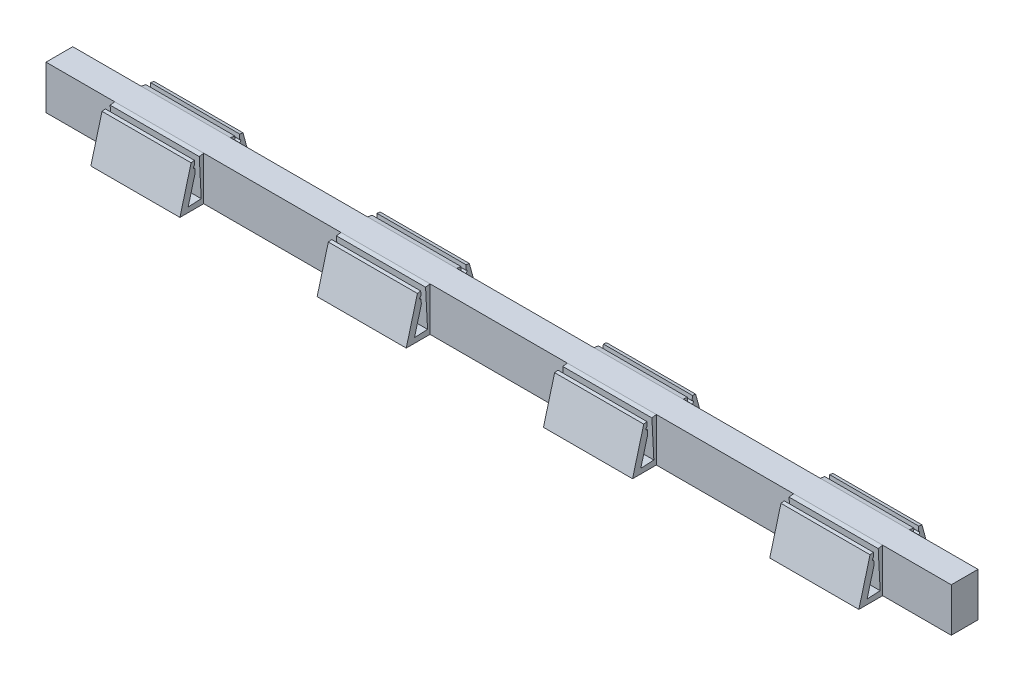
SolidWorks part; units mm, degrees
ref_plane "Front Plane" through (0, 0, 0) normal (0, 0, 1) x (1, 0, 0)
ref_plane "Top Plane" through (0, 0, 0) normal (0, 1, 0) x (1, 0, 0)
ref_plane "Right Plane" through (0, 0, 0) normal (1, 0, 0) x (0, 0, -1)
sketch "Sketch1" plane through (0, 0, 0) normal (1, 0, 0) x (0, 0, -1)
  line L0 (3.6311, 0.3059) -> (9.4677, 0) construction
  line L1 (3.904, 5.5131) -> (4.9077, 5.4605) construction
  line L2 (6.2203, 9.4885) -> (6.0816, 6.8415) construction
  line L3 (6.0816, 6.8415) -> (7.6191, 1.1033)
  line L4 (7.6191, 1.1033) -> (4.6874, 1.2569)
  line L5 (4.6874, 1.2569) -> (5.128, 9.664)
  line L6 (5.128, 9.664) -> (4.13, 9.8243)
  line L7 (4.13, 9.8243) -> (3.6311, 0.3059) construction
  line L8 (6.2203, 9.4885) -> (6.1666, 8.4646)
  line L9 (6.1352, 7.8654) -> (6.0816, 6.8415)
  line L10 (6.2203, 9.4885) -> (6.9569, 9.3702)
  line L11 (6.9569, 9.3702) -> (9.4677, 0)
  line L12 (6.1532, 1.1801) -> (6.1006, 0.1765) construction
  line L13 (1.128, 0) -> (1.128, 7.6812) construction
  line L14 (-3.8973, 1.1801) -> (-3.8447, 0.1765) construction
  line L15 (-5.3632, 1.1033) -> (-2.4314, 1.2569)
  line L16 (-3.9644, 9.4885) -> (-3.8256, 6.8415) construction
  line L17 (-1.6481, 5.5131) -> (-2.6517, 5.4605) construction
  line L18 (-1.3752, 0.3059) -> (-7.2117, 0) construction
  line L19 (-4.701, 9.3702) -> (-7.2117, 0)
  line L20 (-3.9644, 9.4885) -> (-4.701, 9.3702)
  line L21 (-3.8793, 7.8654) -> (-3.8256, 6.8415)
  line L22 (-3.9644, 9.4885) -> (-3.9107, 8.4646)
  line L23 (-1.874, 9.8243) -> (-1.3752, 0.3059) construction
  line L24 (-2.872, 9.664) -> (-1.874, 9.8243)
  line L25 (-2.4314, 1.2569) -> (-2.872, 9.664)
  line L26 (-3.8256, 6.8415) -> (-5.3632, 1.1033)
  line L27 (-1.874, 9.8243) -> (4.13, 9.8243)
  line L28 (-7.2117, 0) -> (-2.3656, 0)
  line L29 (-2.4314, 1.2569) -> (-2.3656, 0)
  line L30 (4.6874, 1.2569) -> (4.6215, 0)
  line L31 (-2.3656, 0) -> (4.6215, 0)
  line L32 (4.6215, 0) -> (9.4677, 0)
  arc A0 (6.1666, 8.4646) -> (6.1352, 7.8654) centre (6.1509, 8.165) cw
  arc A1 (-3.9107, 8.4646) -> (-3.8793, 7.8654) centre (-3.895, 8.165) ccw
  dimension "D1" = 0.3
  dimension "D2" = 1.1
  dimension "D3" = 72
  dimension "D4" = 1.5
  dimension "D5" = 8
extrude "Clip #1" add sketch "Sketch1" along normal mid plane 20 contours L28 L19 L20 L22 A1 L21 L26 L15 L25 L24 L27 L6 L5 L4 L3 L9 A0 L8 L10 L11 L32 L31
sketch "Sketch4" plane through (0, 0, 0) normal (1, 0, 0) x (0, 0, -1)
  line L0 (-1.874, 9.8243) -> (-1.874, 0)
  line L1 (-2.3656, 0) -> (4.6215, 0) construction
  line L2 (-1.874, 9.8243) -> (4.13, 9.8243)
  line L3 (4.13, 9.8243) -> (4.13, 0)
  line L4 (4.13, 0) -> (-1.874, 0)
extrude "Center beam" add sketch "Sketch4" along normal blind 177.8 and the other way blind 25.4
sketch "Sketch5" plane through (0, 0, 0) normal (0, 1, 0) x (1, 0, 0)
  line L0 (76.2, -58.3264) -> (76.2, 110.1277) construction
  line L1 (25.4, 19.5305) -> (25.4, 187.9846) construction
  line L2 (127, 16.9825) -> (127, 185.4366) construction
  line L3 (177.8, 22.3617) -> (177.8, 190.8158) construction
  dimension "D1" = 25.4
  dimension "D2" = 50.8
  dimension "D3" = 50.8
  dimension "D4" = 50.8
sketch3d "3DSketch2" plane through (0, 0, 0) normal (0, 0, 1) x (1, 0, 0)
  dimension "D1" = 25.4
sketch "Sketch6" plane through (25.4, 0, 0) normal (1, 0, 0) x (0, 0, -1)
  line L0 (7.6191, 1.1033) -> (4.6874, 1.2569) construction
  line L5 (6.0816, 6.8415) -> (7.6191, 1.1033) construction
  line L6 (6.1352, 7.8654) -> (6.0816, 6.8415) construction
  line L7 (6.2203, 9.4885) -> (6.1666, 8.4646) construction
  line L8 (6.2203, 9.4885) -> (6.9569, 9.3702) construction
  line L9 (6.9569, 9.3702) -> (9.4677, 0) construction
  line L10 (4.6215, 0) -> (9.4677, 0) construction
  line L11 (4.6874, 1.2569) -> (5.128, 9.664) construction
  line L12 (5.128, 9.664) -> (4.13, 9.8243) construction
  line L13 (-1.874, 9.8243) -> (4.13, 9.8243) construction
  line L14 (-2.872, 9.664) -> (-1.874, 9.8243) construction
  line L15 (-2.4314, 1.2569) -> (-2.872, 9.664) construction
  line L16 (4.6874, 1.2569) -> (4.6215, 0) construction
  line L17 (-7.2117, 0) -> (-2.3656, 0) construction
  line L18 (-4.701, 9.3702) -> (-7.2117, 0) construction
  line L19 (-3.9644, 9.4885) -> (-4.701, 9.3702) construction
  line L20 (-3.9644, 9.4885) -> (-3.9107, 8.4646) construction
  line L21 (-3.8793, 7.8654) -> (-3.8256, 6.8415) construction
  line L22 (-3.8256, 6.8415) -> (-5.3632, 1.1033) construction
  line L23 (-5.3632, 1.1033) -> (-2.4314, 1.2569) construction
  line L24 (-2.4314, 1.2569) -> (-2.3656, 0) construction
  line L25 (-2.3656, 0) -> (4.6215, 0) construction
  line L26 (7.6191, 1.1033) -> (4.6874, 1.2569)
  line L27 (6.0816, 6.8415) -> (7.6191, 1.1033)
  line L28 (6.1352, 7.8654) -> (6.0816, 6.8415)
  line L29 (6.2203, 9.4885) -> (6.1666, 8.4646)
  line L30 (6.2203, 9.4885) -> (6.9569, 9.3702)
  line L31 (6.9569, 9.3702) -> (9.4677, 0)
  line L32 (4.6215, 0) -> (9.4677, 0)
  line L33 (4.6874, 1.2569) -> (5.128, 9.664)
  line L34 (5.128, 9.664) -> (4.13, 9.8243)
  line L35 (-1.874, 9.8243) -> (4.13, 9.8243)
  line L36 (-2.872, 9.664) -> (-1.874, 9.8243)
  line L37 (-2.4314, 1.2569) -> (-2.872, 9.664)
  line L38 (4.6874, 1.2569) -> (4.6215, 0) construction
  line L39 (-7.2117, 0) -> (-2.3656, 0)
  line L40 (-4.701, 9.3702) -> (-7.2117, 0)
  line L41 (-3.9644, 9.4885) -> (-4.701, 9.3702)
  line L42 (-3.9644, 9.4885) -> (-3.9107, 8.4646)
  line L43 (-3.8793, 7.8654) -> (-3.8256, 6.8415)
  line L44 (-3.8256, 6.8415) -> (-5.3632, 1.1033)
  line L45 (-5.3632, 1.1033) -> (-2.4314, 1.2569)
  line L46 (-2.4314, 1.2569) -> (-2.3656, 0) construction
  line L47 (-2.3656, 0) -> (4.6215, 0)
  arc A0 (6.1352, 7.8654) -> (6.1666, 8.4646) centre (6.1509, 8.165) ccw construction
  arc A1 (-3.9107, 8.4646) -> (-3.8793, 7.8654) centre (-3.895, 8.165) ccw construction
  arc A2 (6.1352, 7.8654) -> (6.1666, 8.4646) centre (6.1509, 8.165) ccw
  arc A3 (-3.9107, 8.4646) -> (-3.8793, 7.8654) centre (-3.895, 8.165) ccw
extrude "Boss-Extrude9" [suppressed] add sketch "Sketch6" along normal mid plane 20 contours L37 L36 L35 L34 L33 L26 L27 L28 A2 L29 L30 L31 L32 L47 L39 L40 L41 L42 A3 L43 L44 L45
pattern_linear "LPattern1" count 4 spacing 50.8 along (1, 0, 0) of "Clip #1"
